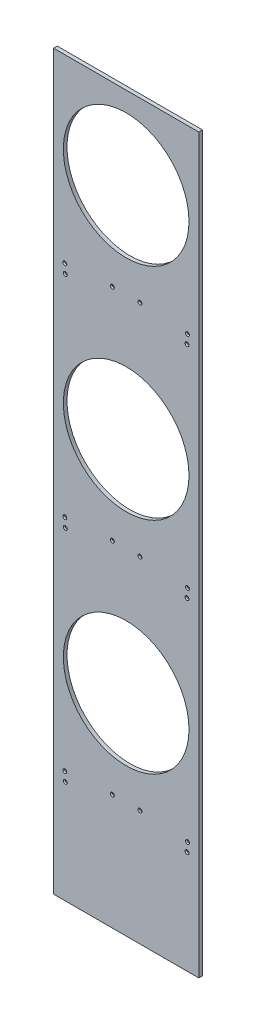
SolidWorks part; units mm, degrees
material "Pine"
ref_plane "Front Plane" through (0, 0, 0) normal (0, 0, 1) x (1, 0, 0)
ref_plane "Top Plane" through (0, 0, 0) normal (0, 1, 0) x (1, 0, 0)
ref_plane "Right Plane" through (0, 0, 0) normal (1, 0, 0) x (0, 0, -1)
sketch "Sketch1" plane through (0, 0, 0) normal (0, 0, 1) x (1, 0, 0)
  line L0 (2118.36, -1353.5651) -> (2118.36, -655.0651) construction
  line L1 (2118.36, 1034.0349) -> (2588.26, 1034.0349)
  line L2 (2118.36, 1034.0349) -> (2118.36, -1353.5651)
  line L3 (2118.36, -1353.5651) -> (2588.26, -1353.5651)
  line L4 (2588.26, 1034.0349) -> (2588.26, -1353.5651)
  line L5 (2118.36, -1353.5651) -> (2118.36, 56.1349) construction
  line L6 (2118.36, -1353.5651) -> (2118.36, 772.4149) construction
  line L7 (2353.31, -1353.5651) -> (2353.31, 1231.1371) construction
  circle A0 centre (2353.31, -655.0651) radius 203.2
  circle A1 centre (2353.31, 56.1349) radius 203.2
  circle A2 centre (2353.31, 767.3349) radius 203.2
  dimension "D6" = 406.4
  dimension "D4" = 1409.7
  dimension "D5" = 2120.9
  dimension "D1" = 2387.6
  dimension "D2" = 469.9
  dimension "D3" = 698.5
extrude "Boss-Extrude1" add sketch "Sketch1" along normal blind 11.9062
hole_wizard "CSK for 1/4 Flat Head Machine Screw1" positions "3DSketch1" profile "Sketch2" countersink size "1/4" standard "ANSI Inch" end condition through all
sketch3d "3DSketch1"
  line L0 (2118.36, -1353.5651, 11.9062) -> (2588.26, -1353.5651, 11.9062) construction
  line L1 (2588.26, -1353.5651, 11.9062) -> (2588.26, 1034.0349, 11.9062) construction
  line L2 (2118.36, 1034.0349, 11.9062) -> (2118.36, -1353.5651, 11.9062) construction
  point P0 (2154.8725, -972.5651, 11.9062)
  point P2 (2156.46, -1001.7751, 11.9062)
  point P4 (2308.86, -961.4526, 11.9062)
  point P6 (2397.76, -961.4526, 11.9062)
  point P8 (2550.16, -1001.7751, 11.9062)
  point P10 (2551.7475, -972.5651, 11.9062)
  point P12 (2154.8725, -261.3651, 11.9062)
  point P14 (2156.46, -290.5751, 11.9062)
  point P16 (2308.86, -250.2526, 11.9062)
  point P18 (2397.76, -250.2526, 11.9062)
  point P20 (2550.16, -290.5751, 11.9062)
  point P22 (2551.7475, -261.3651, 11.9062)
  point P24 (2154.8725, 449.8349, 11.9062)
  point P26 (2156.46, 420.6249, 11.9062)
  point P28 (2308.86, 460.9474, 11.9062)
  point P30 (2397.76, 460.9474, 11.9062)
  point P32 (2550.16, 420.6249, 11.9062)
  point P34 (2551.7475, 449.8349, 11.9062)
  dimension "D1" = 392.1125
  dimension "D2" = 381
  dimension "D3" = 351.79
  dimension "D4" = 36.5125
  dimension "D5" = 433.3875
  dimension "D6" = 431.8
  dimension "D7" = 279.4
  dimension "D8" = 1092.2
  dimension "D9" = 1062.99
  dimension "D10" = 1103.3125
  dimension "D11" = 1803.4
  dimension "D12" = 1774.19
  dimension "D13" = 1814.5125
  dimension "D14" = 38.1
  dimension "D15" = 190.5
  dimension "D16" = 36.5125
  dimension "D17" = 38.1
  dimension "D18" = 190.5
  dimension "D19" = 279.4
  dimension "D20" = 431.8
  dimension "D21" = 433.3875
sketch "Sketch2" plane through (2154.8725, -972.5651, 11.9062) normal (1, 0, 0) x (0, -1, 0)
  line L0 (0, 0) -> (0, 11.9062)
  line L1 (0, 11.9062) -> (3.3782, 11.9062)
  line L2 (3.3782, 11.9062) -> (3.3782, 3.5209)
  line L3 (3.3782, 3.5209) -> (6.4389, 0)
  line L5 (6.4389, 0) -> (0, 0)
  line L6 (-3.3782, 3.5209) -> (-6.4389, 0) construction
  line L11 (0, -6.35) -> (0, 107.95) construction
  dimension "Thru Hole Dia." = 6.7564
  dimension "Thru Hole Depth" = 11.9062
  dimension "Near C'Sink Dia." = 12.8778
  dimension "Near C'Sink Angle" = 82
sketch "Sketch4" plane through (0, 0, 11.9062) normal (0, 0, 1) x (1, 0, 0)
  line L0 (2588.26, -1353.5651) -> (2588.26, 1034.0349) construction
  line L1 (2118.36, -1353.5651) -> (2588.26, -1353.5651)
  line L2 (2118.36, -1353.5651) -> (2118.36, -1335.3088)
  line L3 (2118.36, -1335.3088) -> (2588.26, -1335.3088)
  line L4 (2588.26, -1353.5651) -> (2588.26, -1335.3088)
  dimension "D1" = 18.2562
extrude "Cut-Extrude1" cut sketch "Sketch4" against normal through all
